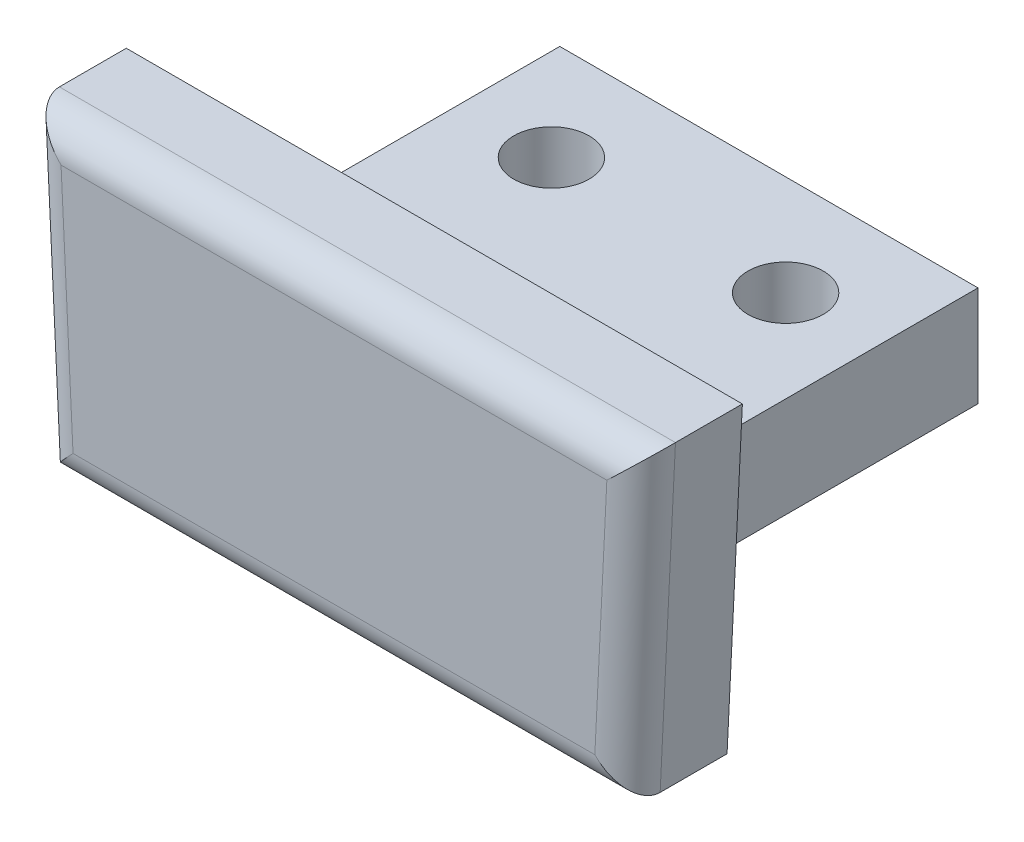
SolidWorks part; units mm, degrees
ref_plane "Front Plane" through (0, 0, 0) normal (0, 0, 1) x (1, 0, 0)
ref_plane "Top Plane" through (0, 0, 0) normal (0, 1, 0) x (1, 0, 0)
ref_plane "Right Plane" through (0, 0, 0) normal (1, 0, 0) x (0, 0, -1)
sketch "Sketch1" plane through (0, 0, 0) normal (0, 1, 0) x (1, 0, 0)
  line L1 (0, 0) -> (25, 0)
  line L2 (0, 0) -> (0, 26)
  line L3 (0, 26) -> (25, 26)
  line L4 (25, 0) -> (25, 26)
  dimension "D1" = 25
  dimension "D2" = 26
extrude "Boss-Extrude1" add sketch "Sketch1" along normal blind 6
sketch "Sketch2" plane through (0, 0, 0) normal (0, -1, 0) x (1, 0, 0)
  line L0 (12.5, 0) -> (12.5, -26) construction
  line L1 (0, 0) -> (25, 0) construction
  line L2 (25, -26) -> (0, -26) construction
  circle A0 centre (5.5, -20) radius 2.25
  circle A1 centre (19.5, -20) radius 2.25
  dimension "D1" = 7
  dimension "D2" = 6
  dimension "D3" = 4.5
extrude "Cut-Extrude1" cut sketch "Sketch2" against normal blind 6
sketch "Sketch4" plane through (0, 0, 0) normal (0, -1, 0) x (-1, 0, 0)
  line L0 (-25, 0) -> (-25, 26) construction
  line L1 (0, 0) -> (-25, 0)
  line L2 (0, 0) -> (0, 6)
  line L3 (0, 6) -> (-25, 6)
  line L4 (-25, 0) -> (-25, 6)
  dimension "D1" = 6
extrude "Boss-Extrude2" add sketch "Sketch4" along normal blind 5.62
sketch "Sketch5" plane through (0, 0, 0) normal (0, 0, 1) x (1, 0, 0)
  line L0 (25, -5.62) -> (0, -5.62) construction
  line L5 (-5, -5.62) -> (30, -5.62)
  line L7 (-5.9133, 12.95) -> (30.915, 12.95)
  line L10 (30, -5.62) -> (30.915, 12.95)
  line L11 (0, 6) -> (25, 6) construction
  line L12 (12.5008, 12.95) -> (12.5, -5.62) construction
  line L13 (-5.9133, 12.95) -> (-5, -5.62)
  point P8 (12.5, -5.62)
  point P10 (12.5, 6)
  dimension "D1" = 35
  dimension "D2" = 36.8283
  dimension "D3" = 6.95
  dimension "D4" = 0
  dimension "D5" = 17.5
  dimension "D6" = 18.415
extrude "Boss-Extrude3" add sketch "Sketch5" against normal blind 6
fillet "Fillet1" radius 2 4 edges at (12.5008, 12.95, 0) (30.4575, 3.665, 0) (12.5, -5.62, 0) (-5.4567, 3.665, 0)
